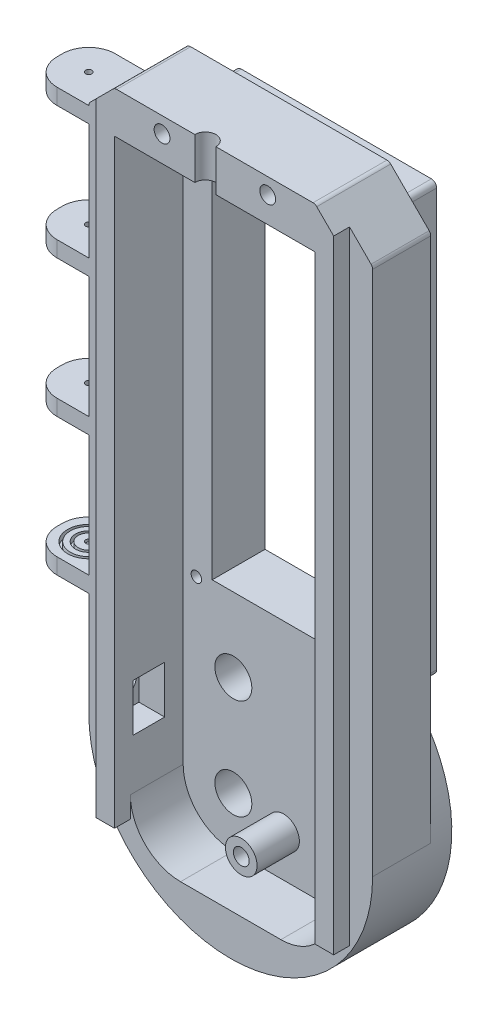
SolidWorks part; units mm, degrees
ref_plane "Alzado" through (0, 0, 0) normal (0, 0, 1) x (1, 0, 0)
ref_plane "Planta" through (0, 0, 0) normal (0, 1, 0) x (1, 0, 0)
ref_plane "Vista lateral" through (0, 0, 0) normal (1, 0, 0) x (0, 0, -1)
sketch "Croquis1" plane through (0, 0, 0) normal (0, 0, 1) x (1, 0, 0)
  line L1 (-19, -40.5) -> (19, -40.5)
  line L2 (-19, -40.5) -> (-19, 40.5)
  line L3 (-19, 40.5) -> (19, 40.5)
  line L4 (19, -40.5) -> (19, 40.5)
  line L5 (-19, -40.5) -> (19, 40.5) construction
  line L6 (-19, 40.5) -> (19, -40.5) construction
  line L7 (-19, -40.5) -> (19, -40.5)
  line L8 (-19, -40.5) -> (-19, -78.5)
  line L9 (-19, -78.5) -> (19, -78.5)
  line L10 (19, -40.5) -> (19, -78.5)
  line L13 (-13.5, 36) -> (13.5, 36)
  line L28 (13.5, 36) -> (13.5, -36)
  line L29 (-13.5, 36) -> (-13.5, -36)
  line L30 (-13.5, -36) -> (13.5, -36)
  circle A0 centre (-9.5, -50) radius 3.5
  circle A1 centre (9.5, -59.5) radius 3.5
  circle A2 centre (-9.5, -69) radius 3.5
  arc A3 (19, -40.5) -> (-19, -40.5) centre (0, -59.5) cw
  point P0 (0, 0)
  point P27 (9.5, -63)
  point P30 (9.5, -54.5)
  point P34 (-13.5, 0)
extrude "Saliente-Extruir1" add sketch "Croquis1" along normal blind 5 contours L1 L4 L3 L2 L30 L29 L13 L28 | L10 L1 L8 L9 A2 A1 A0 | A3 L10 | A3 L9 | A3 L8 region at (-18.1053, 0, 0) region at (0.2752, -59.5, 0) region at (-22.1912, -59.5, 0) region at (22.1912, -59.5, 0) region at (0, -81.6912, 0)
sketch "Croquis2" plane through (0, 0, 0) normal (0, 0, -1) x (-1, 0, 0)
  line L0 (-19, 40.5) -> (19, 40.5)
  line L1 (19, -40.5) -> (-19, -40.5)
  line L2 (-19, -40.5) -> (-19, 40.5)
  line L4 (19, -40.5) -> (19, 40.5)
  line L5 (-13.5, 36) -> (-13.5, -36)
  line L7 (-13.5, -36) -> (13.5, -36)
  line L8 (13.5, -36) -> (13.5, 36)
  line L9 (13.5, 36) -> (-13.5, 36)
extrude "Saliente-Extruir2" add sketch "Croquis2" along normal blind 5
sketch "Croquis3" plane through (0, 0, 5) normal (0, 0, 1) x (1, 0, 0)
  line L0 (26.8701, -59.5) -> (26.8701, 40.5)
  line L1 (19, -59.5) -> (19, 40.5)
  line L2 (19, 40.5) -> (-19, 40.5)
  line L3 (-19, 40.5) -> (-19, -59.5)
  line L4 (26.8701, 40.5) -> (19, 48.3701)
  line L5 (19, 48.3701) -> (-19, 48.3701)
  line L6 (-19, 48.3701) -> (-26.8701, 40.5)
  line L7 (-26.8701, 40.5) -> (-26.8701, -59.5)
  arc A2 (-19, -59.5) -> (19, -59.5) centre (0, -59.5) ccw
  arc A3 (-26.8701, -59.5) -> (26.8701, -59.5) centre (0, -59.5) ccw
extrude "Saliente-Extruir9" add sketch "Croquis3" against normal blind 1
sketch "Croquis4" plane through (0, 0, 4) normal (0, 0, -1) x (-1, 0, 0)
  line L0 (-19, 40.5) -> (-19, -40.5)
  line L1 (-19, 40.5) -> (19, 40.5)
  line L2 (19, 40.5) -> (19, -40.5)
  line L3 (14, -77) -> (-14, -77)
  line L4 (-19, -72) -> (-19, -41.338)
  line L5 (19, -72) -> (19, -40.5)
  line L6 (-26.8701, 40.5) -> (-19, 48.3701)
  line L7 (-19, 48.3701) -> (19, 48.3701)
  line L8 (19, 48.3701) -> (26.8701, 40.5)
  line L9 (26.8701, 40.5) -> (26.8701, -59.5)
  line L10 (-26.8701, 40.5) -> (-26.8701, -59.5)
  arc A0 (-19, -40.5) -> (-26.8701, -59.5) centre (0, -59.5) ccw construction
  arc A1 (-14, -77) -> (-19, -72) centre (-14, -72) cw
  arc A2 (14, -77) -> (19, -72) centre (14, -72) ccw
  arc A3 (-19, -40.5) -> (19, -40.5) centre (0, -59.5) ccw construction
  arc A4 (-26.8701, -59.5) -> (26.8701, -59.5) centre (0, -59.5) ccw
  arc M1 (19, -40.5) -> (26.8701, -59.5) centre (0, -59.5) cw
  line M2 (26.8701, -59.5) -> (26.8701, 40.5)
  line M3 (26.8701, 40.5) -> (19, 48.3701)
  line M4 (19, 48.3701) -> (-19, 48.3701)
  line M5 (-19, 48.3701) -> (-26.8701, 40.5)
  line M6 (-26.8701, 40.5) -> (-26.8701, -59.5)
  arc M7 (-26.8701, -59.5) -> (-19, -40.5) centre (0, -59.5) cw
  line M8 (-19, -40.5) -> (-19, 40.5)
  line M9 (-19, 40.5) -> (19, 40.5)
  line M10 (19, 40.5) -> (19, -40.5)
  dimension "D1" = 5
extrude "Saliente-Extruir10" add sketch "Croquis4" against normal blind 11 contours M10 M1 M2 M3 M4 M5 M6 M7 M8 M9 region at (20.2052, 0, 4)
sketch "Croquis5" plane through (0, 0, 5) normal (0, 0, 1) x (1, 0, 0)
  line L0 (-19, -59.5) -> (-19, -69)
  line L1 (19, -69) -> (19, -59.5)
  line L2 (9.5, -78.5) -> (-9.5, -78.5)
  line L3 (19, -59.5) -> (19, -40.5)
  line L4 (-19, -59.5) -> (-19, -40.5)
  arc A0 (-19, -40.5) -> (19, -40.5) centre (0, -59.5) ccw
  arc A1 (-9.5, -78.5) -> (-19, -69) centre (-9.5, -69) cw
  arc A2 (9.5, -78.5) -> (19, -69) centre (9.5, -69) ccw
extrude "Saliente-Extruir11" add sketch "Croquis5" along normal blind 10
fillet "Redondeo1" radius 1 4 edges at (-19, -40.5, -2.5) (-19, 40.5, -0.5) (19, 40.5, -0.5) (19, -40.5, -2.5)
fillet "Redondeo2" radius 1 5 edges at (-18.7071, 40.2071, 4) (18.7071, 40.2071, 4) (-19, -0.5, 4) (0, 40.5, 4) (19, -0.5, 4)
fillet "Redondeo3" radius 1 4 edges at (-26.8701, 40.5, 9.5) (-19, 48.3701, 9.5) (26.8701, 40.5, 9.5) (19, 48.3701, 9.5)
sketch "Croquis6" plane through (-26.8701, 0, 0) normal (-1, 0, 0) x (0, 0, 1)
  line L2 (8.5, -50.5) -> (14.5, -50.5)
  line L3 (14.5, -50.5) -> (14.5, -59.5)
  line L4 (14.5, -59.5) -> (8.5, -59.5)
  line L5 (8.5, -50.5) -> (8.5, -59.5)
extrude "Cortar-Extruir1" cut sketch "Croquis6" against normal blind 8
sketch "Croquis7" plane through (-26.8701, 0, 0) normal (-1, 0, 0) x (0, 0, 1)
  line L0 (8.5, -50.5) -> (14.5, -50.5)
  line L1 (14.5, -50.5) -> (14.5, -59.5)
  line L2 (14.5, -59.5) -> (8.5, -59.5)
  line L3 (8.5, -59.5) -> (8.5, -50.5)
  circle A0 centre (11.5, -55) radius 2.5
extrude "Saliente-Extruir12" add sketch "Croquis7" against normal blind 3
sketch "Croquis8" plane through (-26.8701, 0, 0) normal (-1, 0, 0) x (0, 0, 1)
  line L0 (4, 40.0858) -> (4, 37.0858)
  line L1 (4, 39.5) -> (4, -41.5556) construction
  line L2 (4, 37.0858) -> (15, 37.0858)
  line L3 (15, -59.5) -> (15, 40.0858) construction
  line L4 (15, 37.0858) -> (15, 40.0858)
  line L5 (15, 40.0858) -> (4, 40.0858)
  line L6 (9.5, 37.0858) -> (9.5, 15.0858)
  line L7 (9.5, 15.0858) -> (15, 15.0858)
  line L8 (9.5, 15.0858) -> (4, 15.0858)
  line L9 (4, 15.0858) -> (4, 12.0858)
  line L10 (4, 40.0858) -> (4, -59.5) construction
  line L11 (4, 12.0858) -> (15, 12.0858)
  line L12 (15, 12.0858) -> (15, 15.0858)
  line L13 (9.5, 12.0858) -> (9.5, -10.9142)
  line L14 (9.5, -10.9142) -> (15, -10.9142)
  line L15 (15, -10.9142) -> (15, -13.9142)
  line L16 (15, -13.9142) -> (4, -13.9142)
  line L17 (4, -13.9142) -> (4, -10.9142)
  line L18 (4, -10.9142) -> (9.5, -10.9142)
  line L19 (9.5, -13.9142) -> (9.5, -36.9142)
  line L20 (9.5, -36.9142) -> (15, -36.9142)
  line L21 (15, -36.9142) -> (15, -39.9142)
  line L22 (15, -39.9142) -> (4, -39.9142)
  line L23 (4, -39.9142) -> (4, -36.9142)
  line L24 (4, -36.9142) -> (9.5, -36.9142)
  line M2 (15, -59.5) -> (15, 40.0858)
  line M3 (15, 40.0858) -> (4, 40.0858)
  line M4 (4, 40.0858) -> (4, -59.5)
extrude "Saliente-Extruir13" add sketch "Croquis8" along normal blind 11 contours L2 M4 M2 M3 | L11 L7 L8 M4 M2 | L18 L16 L14 M4 M2 | L24 L22 L20 M4 M2 region at (-26.8701, 38.5858, 9.5) region at (-26.8701, 13.5858, 9.5) region at (-26.8701, -12.4142, 9.5) region at (-26.8701, -38.4142, 9.5)
fillet "Redondeo4" radius 5 8 edges at (-37.8701, -38.4142, 4) (-37.8701, -38.4142, 15) (-37.8701, -12.4142, 4) (-37.8701, -12.4142, 15) (-37.8701, 13.5858, 4) (-37.8701, 13.5858, 15) (-37.8701, 38.5858, 4) (-37.8701, 38.5858, 15)
sketch "Croquis9" plane through (0, 40.0858, 0) normal (0, 1, 0) x (1, 0, 0)
  circle A0 centre (-32.3701, -9.5) radius 0.6
extrude "Cortar-Extruir2" cut sketch "Croquis9" against normal blind 80
sketch "Croquis10" plane through (0, -39.9142, 0) normal (0, -1, 0) x (1, 0, 0)
  circle A0 centre (-32.3701, 9.5) radius 0.6
extrude "Saliente-Extruir14" add sketch "Croquis10" against normal blind 2.5
sketch "Croquis11" plane through (0, -36.9142, 0) normal (0, 1, 0) x (1, 0, 0)
  circle A0 centre (-32.3701, -9.5) radius 2
  circle A1 centre (-32.3701, -9.5) radius 2.5
  circle A2 centre (-32.3701, -9.5) radius 3.5
  circle A3 centre (-32.3701, -9.5) radius 4
extrude "Cortar-Extruir3" cut sketch "Croquis11" against normal blind 1 contours A3 A2 | A1 A0 region at (-34.7993, -36.9142, 9.5) region at (-36.2569, -36.9142, 9.5)
sketch "Croquis13" plane through (0, 0, 15) normal (0, 0, 1) x (1, 0, 0)
  line L0 (19, 40.5) -> (22.5, 40.5)
  line L1 (19, -69) -> (22.5, -69)
  line L2 (22.5, -69) -> (22.5, 40.5)
  line L3 (19, -69) -> (19, 40.5)
  line L5 (22.5, 40.5) -> (22.5, 44.8701)
  line L6 (-19, -69) -> (-19, 40.5)
  line L7 (-22.5, -69) -> (-22.5, 40.5)
  line L8 (-19, -69) -> (-22.5, -69)
  line L9 (-19, 40.5) -> (-22.5, 40.5)
  line L10 (-19, -69) -> (-19, -65.5)
  line L12 (19, -65.5) -> (19, -69)
  line L13 (-22.5, 40.5) -> (-22.5, 44.8701)
  line L14 (-26.5772, 40.7929) -> (-19.2929, 48.0772) construction
  line L15 (-22.5, 44.8701) -> (-19.2929, 48.0772)
  line L16 (-18.5858, 48.3701) -> (18.5858, 48.3701)
  line L19 (22.5, 44.8701) -> (19.2929, 48.0772)
  arc A0 (-19.2929, 48.0772) -> (-18.5858, 48.3701) centre (-18.5858, 47.3701) cw
  arc A1 (19.2929, 48.0772) -> (18.5858, 48.3701) centre (18.5858, 47.3701) ccw
  line M1 (19, 40.5) -> (19, -69)
  line M5 (-19, -69) -> (-19, 40.5)
  line M6 (-19, 40.5) -> (19, 40.5)
  line M14 (26.5772, 40.7929) -> (19.2929, 48.0772)
  arc M15 (19.2929, 48.0772) -> (18.5858, 48.3701) centre (18.5858, 47.3701) ccw
  line M16 (18.5858, 48.3701) -> (-18.5858, 48.3701)
  arc M17 (-18.5858, 48.3701) -> (-19.2929, 48.0772) centre (-18.5858, 47.3701) ccw
  line M18 (-19.2929, 48.0772) -> (-26.5772, 40.7929)
extrude "Saliente-Extruir15" add sketch "Croquis13" along normal blind 3 contours L6 L9 L7 L8 M5 | L1 L2 L0 L3 M1 | L13 L9 L0 L5 M6 M14 M15 M16 M17 M18 region at (0, 44.3353, 15) region at (20.75, -14.25, 15) region at (-20.75, -14.25, 15)
sketch "Croquis14" plane through (0, 0, 4) normal (0, 0, -1) x (-1, 0, 0)
  circle A0 centre (10, 45.3701) radius 1.5
  circle A1 centre (-10, 45.3701) radius 1.5
extrude "Cortar-Extruir4" cut sketch "Croquis14" against normal blind 14
sketch "Croquis16" plane through (0, -69, 0) normal (0, -1, 0) x (-1, 0, 0)
  line L1 (22.5, -15) -> (19, -15)
  line L2 (22.5, -15) -> (22.5, -18)
  line L3 (22.5, -18) -> (19, -18)
  line L4 (-19, -15) -> (-22.5, -15)
  line L5 (-19, -15) -> (-19, -18)
  line L6 (-19, -18) -> (-22.5, -18)
  line L7 (-22.5, -15) -> (-22.5, -18)
  line L8 (19, -15) -> (19, -18)
extrude "Saliente-Extruir16" add sketch "Croquis16" along normal blind 4
sketch "Croquis25" plane through (0, 0, 18) normal (0, 0, 1) x (1, 0, 0)
  line L0 (-10, 45.3701) -> (10, 45.3701)
  line L1 (0, 45.3701) -> (0, -70.6299)
  circle A0 centre (0, -70.6299) radius 3
  circle A1 centre (0, -70.6299) radius 1.5
extrude "Saliente-Extruir21" add sketch "Croquis25" against normal blind 18 contours A1 A0 region at (2.0613, -68.5686, 18)
sketch "Croquis26" plane through (0, 0, 18) normal (0, 0, 1) x (1, 0, 0)
  circle A0 centre (0, -70.6299) radius 1.5
extrude "Cortar-Extruir7" cut sketch "Croquis26" against normal blind 18
sketch "Croquis28" plane through (0, 0, 5) normal (0, 0, 1) x (1, 0, 0)
  circle A0 centre (-16.5, 38) radius 1
  circle A1 centre (14.5, 38) radius 1
  circle A2 centre (14.5, -37) radius 1
  circle A3 centre (-16.5, -37) radius 1
extrude "Cortar-Extruir8" cut sketch "Croquis28" against normal blind 4
sketch "Croquis29" plane through (0, 0, 18) normal (0, 0, 1) x (1, 0, 0)
  circle A0 centre (0, -70.6299) radius 1.5
  circle A1 centre (0, -70.6299) radius 3
extrude "Cortar-Extruir9" cut sketch "Croquis29" against normal blind 5
sketch "Croquis30" plane through (0, 0, 18) normal (0, 0, 1) x (1, 0, 0)
  line L3 (-1.8, 45.3701) -> (-1.8, 40.5)
  line L5 (-19, 40.5) -> (19, 40.5) construction
  line L6 (-1.8, 40.5) -> (0.2, 40.5)
  line L8 (0.2, 40.5) -> (0.2, 48.3701)
  line L9 (18.5858, 48.3701) -> (-18.5858, 48.3701) construction
  line L10 (0.2, 48.3701) -> (-1.8, 48.3701)
  line L11 (-1.8, 48.3701) -> (-1.8, 45.3701)
revolve "Cortar-Revolución1" cut sketch "Croquis30" angle 360 about L3
